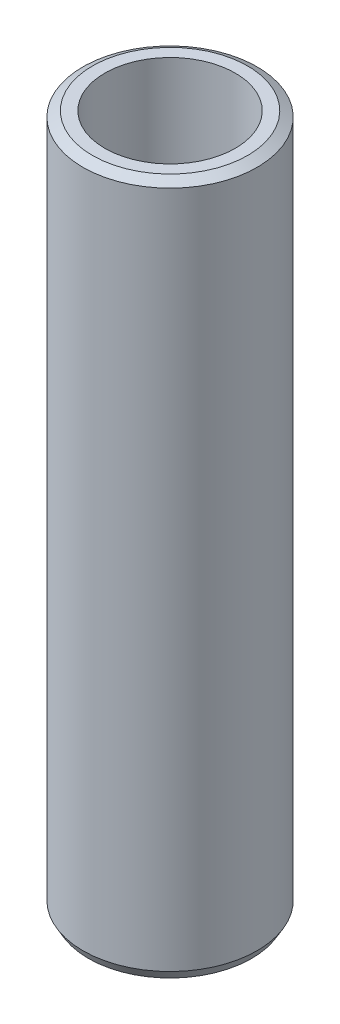
SolidWorks part; units mm, degrees
ref_plane "Front Plane" through (0, 0, 0) normal (0, 0, 1) x (1, 0, 0)
ref_plane "Top Plane" through (0, 0, 0) normal (0, 1, 0) x (1, 0, 0)
ref_plane "Right Plane" through (0, 0, 0) normal (1, 0, 0) x (0, 0, -1)
sketch "Sketch1" plane through (0, 0, 0) normal (0, 1, 0) x (1, 0, 0)
  circle A0 centre (0, 0) radius 35
  dimension "SHAFT_OD" = 70
extrude "Boss-Extrude1" add sketch "Sketch1" along normal blind 278.6067
sketch "Sketch2" plane through (0, 0, 0) normal (0, 1, 0) x (1, 0, 0)
  circle A0 centre (0, 0) radius 26.2025
  dimension "BORE_D" = 52.4051
extrude "Cut-Extrude1" cut sketch "Sketch2" along normal through all
chamfer "Chamfer1" distance 2.2077 angle 60 2 edges at (0, 278.6067, 35) (0, 0, 35) first distance on face at (0, 278.6067, 35) first distance on face at (0, 0, 26.2025)
